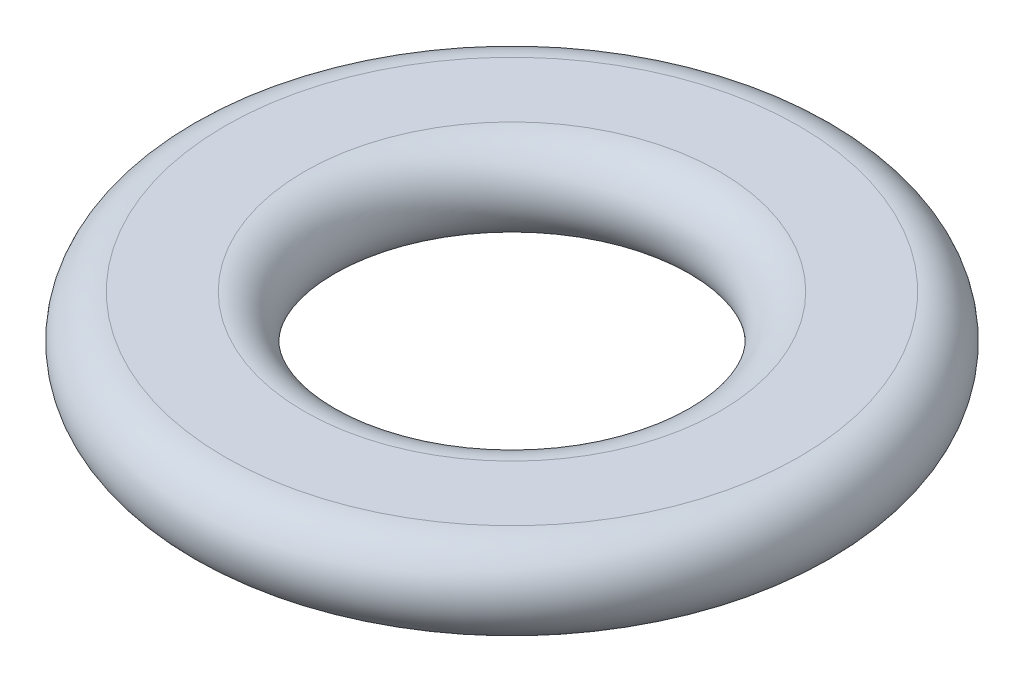
SolidWorks part; units mm, degrees
material "Silicon Rubber"
ref_plane "Front Plane" through (0, 0, 0) normal (0, 0, 1) x (1, 0, 0)
ref_plane "Top Plane" through (0, 0, 0) normal (0, 1, 0) x (1, 0, 0)
ref_plane "Right Plane" through (0, 0, 0) normal (1, 0, 0) x (0, 0, -1)
ref_axis "CentralAxis" through (0, 0.715, 0) along (0, -1, 0)
sketch "ProfileS" plane through (0, 0, 0) normal (0, 0, 1) x (1, 0, 0)
  line L0 (3.15, 0) -> (4.35, 0) construction
  line L1 (3.15, 0.65) -> (4.35, 0.65)
  line L2 (3.15, -0.65) -> (4.35, -0.65)
  line L3 (0, 0.65) -> (0, -0.65) construction
  arc A0 (3.15, 0.65) -> (3.15, -0.65) centre (3.15, 0) ccw
  arc A1 (4.35, -0.65) -> (4.35, 0.65) centre (4.35, 0) ccw
  point P2 (3.75, 0)
  point P8 (2.5, 0)
  point P9 (5, 0)
  dimension "Height" = 1.3
  dimension "ID" = 5
  dimension "OD" = 10
revolve "Profile" add sketch "ProfileS" angle 360 about L3
